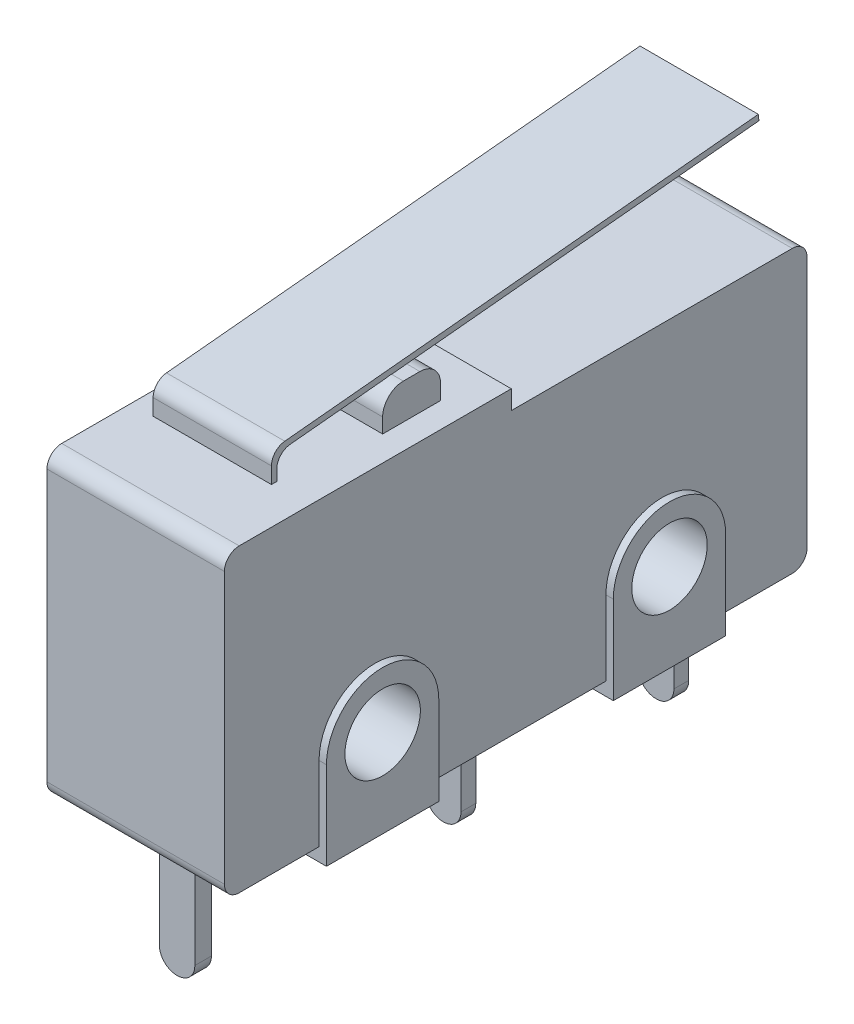
SolidWorks part; units mm, degrees
ref_plane "Front Plane" through (0, 0, 0) normal (0, 0, 1) x (1, 0, 0)
ref_plane "Top Plane" through (0, 0, 0) normal (0, 1, 0) x (1, 0, 0)
ref_plane "Right Plane" through (0, 0, 0) normal (1, 0, 0) x (0, 0, -1)
sketch "Sketch1" plane through (0, 0, 0) normal (1, 0, 0) x (0, 0, -1)
  line L0 (-37.3731, 0) -> (-34.6731, 0)
  line L1 (-37.8731, 0.5) -> (-37.8731, 9.66)
  line L2 (-37.3731, 10.16) -> (-28.1731, 10.16)
  line L3 (-28.1731, 10.16) -> (-28.1731, 9.52)
  line L4 (-28.1731, 9.52) -> (-18.6731, 9.52)
  line L5 (-18.1731, 9.02) -> (-18.1731, 0.5)
  line L6 (-34.6731, 0) -> (-34.6731, -0.45)
  line L7 (-34.6731, -0.45) -> (-30.8731, -0.45)
  line L8 (-30.8731, -0.45) -> (-30.8731, 0)
  line L9 (-30.8731, 0) -> (-24.9731, 0)
  line L10 (-24.9731, 0) -> (-24.9731, -0.45)
  line L11 (-24.9731, -0.45) -> (-21.1731, -0.45)
  line L12 (-21.1731, -0.45) -> (-21.1731, 0)
  line L13 (-21.1731, 0) -> (-18.6731, 0)
  line L14 (-32.7731, -0.45) -> (-32.7731, 2.9938) construction
  line L15 (-23.0731, -0.45) -> (-23.0731, 2.9938) construction
  arc A0 (-18.6731, 9.52) -> (-18.1731, 9.02) centre (-18.6731, 9.02) cw
  arc A1 (-18.6731, 0) -> (-18.1731, 0.5) centre (-18.6731, 0.5) ccw
  arc A2 (-37.3731, 0) -> (-37.8731, 0.5) centre (-37.3731, 0.5) cw
  arc A3 (-37.8731, 9.66) -> (-37.3731, 10.16) centre (-37.3731, 9.66) cw
  circle A4 centre (-32.7731, 2.525) radius 1.275
  circle A5 centre (-23.0731, 2.525) radius 1.275
  point P18 (-23.0731, -0.45)
  point P19 (-18.1731, 9.52)
  point P22 (-18.1731, 0)
  point P25 (-37.8731, 0)
  point P28 (-37.8731, 10.16)
  point P29 (-32.7731, -0.45)
  point P38 (-32.7731, 1.25)
  point P39 (-23.0731, 1.25)
  dimension "D11" = 0.5
  dimension "D12" = 2.55
  dimension "D13" = 2.55
  dimension "D1" = 9.52
  dimension "D2" = 10.16
  dimension "D3" = 3.8
  dimension "D4" = 3.8
  dimension "D5" = 0.45
  dimension "D6" = 0.45
  dimension "D7" = 19.7
  dimension "D8" = 3.2
  dimension "D9" = 9.7
  dimension "D10" = 5.9
  dimension "D14" = 1.7
  dimension "D15" = 1.7
extrude "Boss-Extrude1" add sketch "Sketch1" along normal blind 6.5
sketch "Sketch2" plane through (0, 10.16, 0) normal (0, 1, 0) x (1, 0, 0)
  line L0 (6.5, -28.1731) -> (6.5, -37.3731) construction
  line L1 (5.4, -31.6731) -> (1.87, -31.6731)
  line L2 (5.4, -31.6731) -> (5.4, -29.7131)
  line L3 (5.4, -29.7131) -> (1.87, -29.7131)
  line L4 (1.87, -31.6731) -> (1.87, -29.7131)
  line L5 (5.4, -31.6731) -> (1.87, -29.7131) construction
  line L6 (5.4, -29.7131) -> (1.87, -31.6731) construction
  line L7 (6.5, -37.8731) -> (0, -37.8731) construction
  point P0 (3.635, -30.6931)
  dimension "D1" = 1.96
  dimension "D2" = 3.53
  dimension "D3" = 1.1
  dimension "D4" = 6.2
extrude "Boss-Extrude2" add sketch "Sketch2" along normal blind 1.2
fillet "Fillet1" radius 0.7 2 edges at (3.635, 11.36, 29.7131) (3.635, 11.36, 31.6731)
sketch "Sketch3" plane through (0, 0, 0) normal (0, -1, 0) x (-1, 0, 0)
  line L0 (-3.25, -37.3731) -> (-3.25, -18.1731) construction
  line L1 (-6.5, -37.3731) -> (0, -37.3731) construction
  line L2 (-6.5, -18.1731) -> (0, -18.1731) construction
  line L3 (-6.5, -37.8731) -> (0, -37.8731) construction
  line L4 (-1.65, -36.4731) -> (-4.85, -36.4731)
  line L5 (-1.65, -36.4731) -> (-1.65, -35.9131)
  line L6 (-1.65, -35.9131) -> (-4.85, -35.9131)
  line L7 (-4.85, -36.4731) -> (-4.85, -35.9131)
  line L8 (-1.65, -36.4731) -> (-4.85, -35.9131) construction
  line L9 (-1.65, -35.9131) -> (-4.85, -36.4731) construction
  line L10 (-1.65, -26.9731) -> (-4.85, -26.9731)
  line L11 (-1.65, -26.9731) -> (-1.65, -27.4731)
  line L12 (-1.65, -27.4731) -> (-4.85, -27.4731)
  line L13 (-4.85, -26.9731) -> (-4.85, -27.4731)
  line L14 (-1.65, -26.9731) -> (-4.85, -27.4731) construction
  line L15 (-1.65, -27.4731) -> (-4.85, -26.9731) construction
  line L16 (-1.65, -19.7731) -> (-4.85, -19.7731)
  line L17 (-1.65, -19.7731) -> (-1.65, -20.2731)
  line L18 (-1.65, -20.2731) -> (-4.85, -20.2731)
  line L19 (-4.85, -19.7731) -> (-4.85, -20.2731)
  line L20 (-1.65, -19.7731) -> (-4.85, -20.2731) construction
  line L21 (-1.65, -20.2731) -> (-4.85, -19.7731) construction
  point P6 (-3.25, -36.1931)
  point P11 (-3.25, -27.2231)
  point P16 (-3.25, -20.0231)
  dimension "D1" = 3.2
  dimension "D2" = 0.56
  dimension "D3" = 3.2
  dimension "D4" = 0.5
  dimension "D5" = 3.2
  dimension "D6" = 0.5
  dimension "D7" = 1.6
  dimension "D8" = 1.4
  dimension "D9" = 6.7
extrude "Boss-Extrude3" add sketch "Sketch3" along normal blind 0.9
sketch "Sketch4" plane through (0, -0.9, 0) normal (0, -1, 0) x (-1, 0, 0)
  line L0 (-3.25, -36.4731) -> (-3.25, -19.7731) construction
  line L1 (-4.85, -36.4731) -> (-1.65, -36.4731) construction
  line L2 (-1.65, -19.7731) -> (-4.85, -19.7731) construction
  line L3 (-4.85, -36.4731) -> (-1.65, -36.4731) construction
  line L4 (-2.65, -36.4731) -> (-3.85, -36.4731)
  line L5 (-2.65, -36.4731) -> (-2.65, -35.9131)
  line L6 (-2.65, -35.9131) -> (-3.85, -35.9131)
  line L7 (-3.85, -36.4731) -> (-3.85, -35.9131)
  line L8 (-2.65, -36.4731) -> (-3.85, -35.9131) construction
  line L9 (-2.65, -35.9131) -> (-3.85, -36.4731) construction
  line L10 (-1.65, -35.9131) -> (-4.85, -35.9131) construction
  line L11 (-4.85, -27.4731) -> (-1.65, -27.4731) construction
  line L12 (-3.85, -26.9731) -> (-2.65, -26.9731)
  line L13 (-3.85, -26.9731) -> (-3.85, -27.4731)
  line L14 (-3.85, -27.4731) -> (-2.65, -27.4731)
  line L15 (-2.65, -26.9731) -> (-2.65, -27.4731)
  line L16 (-3.85, -26.9731) -> (-2.65, -27.4731) construction
  line L17 (-3.85, -27.4731) -> (-2.65, -26.9731) construction
  line L18 (-1.65, -26.9731) -> (-4.85, -26.9731) construction
  line L19 (-4.85, -20.2731) -> (-1.65, -20.2731) construction
  line L20 (-3.85, -19.7731) -> (-2.65, -19.7731)
  line L21 (-3.85, -19.7731) -> (-3.85, -20.2731)
  line L22 (-3.85, -20.2731) -> (-2.65, -20.2731)
  line L23 (-2.65, -19.7731) -> (-2.65, -20.2731)
  line L24 (-3.85, -19.7731) -> (-2.65, -20.2731) construction
  line L25 (-3.85, -20.2731) -> (-2.65, -19.7731) construction
  line L26 (-1.65, -19.7731) -> (-4.85, -19.7731) construction
  point P6 (-3.25, -36.1931)
  point P15 (-3.25, -27.2231)
  point P24 (-3.25, -20.0231)
  dimension "D1" = 1.2
  dimension "D2" = 1.2
  dimension "D3" = 1.2
extrude "Boss-Extrude4" add sketch "Sketch4" along normal blind 3.47
fillet "Fillet2" radius 0.59 6 edges at (2.65, -4.37, 36.1931) (3.85, -4.37, 36.1931) (2.65, -4.37, 27.2231) (3.85, -4.37, 27.2231) (3.85, -4.37, 20.0231) (2.65, -4.37, 20.0231)
sketch "Эскиз1" plane through (6.5, 0, 0) normal (1, 0, 0) x (0, 0, -1)
  line L0 (-34.8519, 10.16) -> (-34.8519, 10.9768)
  line L1 (-34.8519, 10.9768) -> (-18.5506, 12.5709)
  line L2 (-18.5506, 12.5709) -> (-18.57, 12.77)
  line L4 (-18.57, 12.77) -> (-35.0331, 11.16)
  line L5 (-35.0331, 11.16) -> (-35.0331, 10.16)
  line L6 (-28.1731, 10.16) -> (-37.3731, 10.16) construction
  line L7 (-35.0331, 10.16) -> (-34.8519, 10.16)
  line L8 (-37.8731, 9.66) -> (-37.8731, 0.5) construction
  line M5 (-28.1731, 10.16) -> (-37.3731, 10.16)
  dimension "D1" = 2.84
  dimension "D2" = 3.25
  dimension "D3" = 1
  dimension "D4" = 0.2
extrude "Бобышка-Вытянуть1" add sketch "Эскиз1" against normal blind 4 from offset 1.5 contours L4 L5 L0 L1 L2 M5 | L2 | L2 region at (6.5, 11.8099, 27.1416) offset against normal yes
fillet "Скругление1" radius 0.5 2 edges at (3, 10.9768, 34.8519) (3, 11.16, 35.0331)
sketch "Sketch6" plane through (6.5, 0, 0) normal (1, 0, 0) x (0, 0, -1)
  line L0 (-34.6731, 2.525) -> (-34.6731, 0)
  line L1 (-30.8731, 2.525) -> (-30.8731, 0)
  line L2 (-24.9731, 2.525) -> (-24.9731, 0)
  line L3 (-21.1731, 2.525) -> (-21.1731, 0)
  line L14 (-18.6731, 9.52) -> (-28.1731, 9.52)
  line L15 (-28.1731, 9.52) -> (-28.1731, 10.16)
  line L16 (-28.1731, 10.16) -> (-37.3731, 10.16)
  line L17 (-37.8731, 9.66) -> (-37.8731, 0.5)
  line L18 (-37.3731, 0) -> (-34.6731, 0)
  line L19 (-34.6731, 0) -> (-34.6731, -0.45)
  line L20 (-34.6731, -0.45) -> (-30.8731, -0.45)
  line L21 (-30.8731, -0.45) -> (-30.8731, 0)
  line L22 (-30.8731, 0) -> (-24.9731, 0)
  line L23 (-24.9731, 0) -> (-24.9731, -0.45)
  line L24 (-24.9731, -0.45) -> (-21.1731, -0.45)
  line L25 (-21.1731, -0.45) -> (-21.1731, 0)
  line L26 (-21.1731, 0) -> (-18.6731, 0)
  line L27 (-18.1731, 0.5) -> (-18.1731, 9.02)
  line L28 (-18.6731, 9.52) -> (-28.1731, 9.52)
  line L29 (-28.1731, 9.52) -> (-28.1731, 10.16)
  line L30 (-28.1731, 10.16) -> (-37.3731, 10.16)
  line L31 (-37.8731, 9.66) -> (-37.8731, 0.5)
  line L32 (-37.3731, 0) -> (-34.6731, 0)
  line L33 (-34.6731, 0) -> (-34.6731, -0.45)
  line L34 (-34.6731, -0.45) -> (-30.8731, -0.45)
  line L35 (-30.8731, -0.45) -> (-30.8731, 0)
  line L36 (-30.8731, 0) -> (-24.9731, 0)
  line L37 (-24.9731, 0) -> (-24.9731, -0.45)
  line L38 (-24.9731, -0.45) -> (-21.1731, -0.45)
  line L39 (-21.1731, -0.45) -> (-21.1731, 0)
  line L40 (-21.1731, 0) -> (-18.6731, 0)
  line L41 (-18.1731, 0.5) -> (-18.1731, 9.02)
  circle A0 centre (-32.7731, 2.525) radius 1.9
  circle A1 centre (-23.0731, 2.525) radius 1.9
  arc A4 (-18.1731, 9.02) -> (-18.6731, 9.52) centre (-18.6731, 9.02) ccw
  arc A5 (-37.3731, 10.16) -> (-37.8731, 9.66) centre (-37.3731, 9.66) ccw
  arc A6 (-37.8731, 0.5) -> (-37.3731, 0) centre (-37.3731, 0.5) ccw
  arc A7 (-18.6731, 0) -> (-18.1731, 0.5) centre (-18.6731, 0.5) ccw
  arc A8 (-18.1731, 9.02) -> (-18.6731, 9.52) centre (-18.6731, 9.02) ccw
  arc A9 (-37.3731, 10.16) -> (-37.8731, 9.66) centre (-37.3731, 9.66) ccw
  arc A10 (-37.8731, 0.5) -> (-37.3731, 0) centre (-37.3731, 0.5) ccw
  arc A11 (-18.6731, 0) -> (-18.1731, 0.5) centre (-18.6731, 0.5) ccw
  arc M20 (-18.1731, 9.02) -> (-18.6731, 9.52) centre (-18.6731, 9.02) ccw
  line M21 (-18.6731, 9.52) -> (-28.1731, 9.52)
  line M22 (-28.1731, 9.52) -> (-28.1731, 10.16)
  line M23 (-28.1731, 10.16) -> (-37.3731, 10.16)
  arc M24 (-37.3731, 10.16) -> (-37.8731, 9.66) centre (-37.3731, 9.66) ccw
  line M25 (-37.8731, 9.66) -> (-37.8731, 0.5)
  arc M26 (-37.8731, 0.5) -> (-37.3731, 0) centre (-37.3731, 0.5) ccw
  line M27 (-37.3731, 0) -> (-34.6731, 0)
  line M31 (-30.8731, 0) -> (-24.9731, 0)
  line M35 (-21.1731, 0) -> (-18.6731, 0)
  arc M36 (-18.6731, 0) -> (-18.1731, 0.5) centre (-18.6731, 0.5) ccw
  line M37 (-18.1731, 0.5) -> (-18.1731, 9.02)
  dimension "D1" = 0
extrude "Extrude1" cut sketch "Sketch6" against normal blind 0.25 contours A1 L3 L0 A0 L1 L2 M35 M36 M37 M20 M21 M22 M23 M24 M25 M26 M27 M31 region at (6.5, 5.4644, 28.2323)
extrude "Extrude2" cut sketch "Sketch" along normal blind 0.25 from surface contours A1 L3 L0 A0 L1 L2 M35 M36 M37 M20 M21 M22 M23 M24 M25 M26 M27 M31 region at (6.5, 5.4644, 28.2323) starting at face at (0, 2.525, 31.4981)
sketch "Sketch" plane through (6.5, 0, 0) normal (1, 0, 0) x (0, 0, -1) same geometry as "Sketch6"
